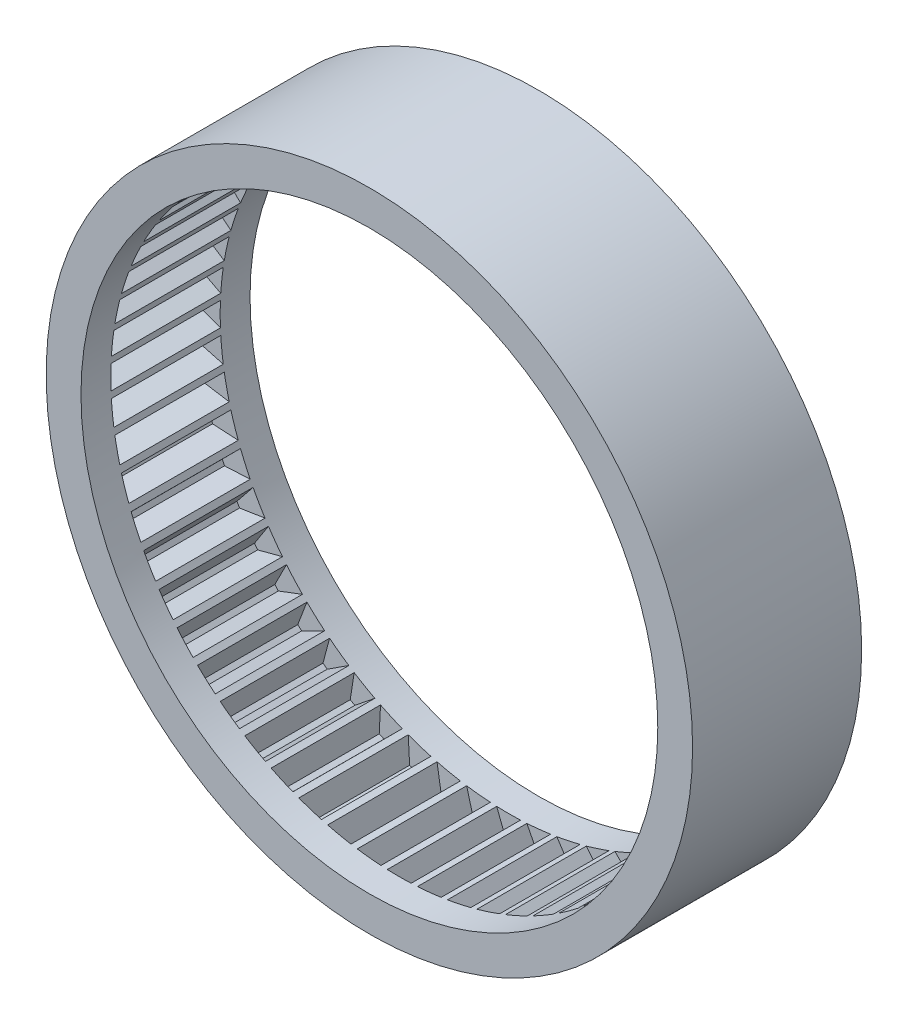
SolidWorks part; units mm, degrees
ref_plane "Front Plane" through (0, 0, 0) normal (0, 0, 1) x (1, 0, 0)
ref_plane "Top Plane" through (0, 0, 0) normal (0, 1, 0) x (1, 0, 0)
ref_plane "Right Plane" through (0, 0, 0) normal (1, 0, 0) x (0, 0, -1)
sketch "Esquisse5" plane through (0, 0, 0) normal (0, 0, 1) x (1, 0, 0)
  circle A0 centre (0, 0) radius 29
  circle A1 centre (0, 0) radius 32.5
  dimension "D1" = 58
  dimension "D2" = 65
extrude "Boss.-Extru.3" add sketch "Esquisse5" against normal blind 17 from offset 18 offset against normal yes
ref_plane "Plan4" through (0, 0, -26.5) normal (0, 0, -1) x (-1, 0, 0)
sketch "Esquisse6" plane through (0, 0, -26.5) normal (0, 0, -1) x (-1, 0, 0)
  line L0 (0, 111.9885) -> (0, -49.2085) construction
  line L1 (1.2196, 28.9208) -> (1.436, 28.9095)
  line L2 (1.436, 28.9095) -> (1.436, 32.2573) construction
  line L3 (1.436, 28.9095) -> (1.436, 28.7372)
  line L4 (1.436, 28.7372) -> (-1.436, 28.7372)
  line L5 (-1.436, 28.7372) -> (-1.436, 28.9095)
  line L6 (-0.2642, 31.39) -> (0.2642, 31.39)
  line L7 (0.2642, 31.39) -> (1.2205, 28.9186)
  line L8 (-0.2642, 31.39) -> (-1.2196, 28.9208)
  line L9 (-1.436, 28.9095) -> (-1.6741, 33.4532) construction
  line L11 (-1.2196, 28.9208) -> (-1.436, 28.9095)
  circle A2 centre (0, 0) radius 29 construction
  point P16 (0, 31.39)
  dimension "D1" = 2.65
  dimension "D2" = 1.3
  dimension "D3" = 31.39
  dimension "D4" = 111.153
  dimension "D5" = 111.153
  dimension "D6" = 114.153
  dimension "D7" = 0.2642
  dimension "D9" = 2.6475
extrude "Enlèv. mat.-Extru.2" cut sketch "Esquisse6" against normal mid plane 11 contours L8 L11 L5 L4 L3 L1 L7 L6 region at (0, 29.7573, -26.5)
ref_axis "Axe2" through (0, 0, -18) along (0, 0, -1)
pattern_circular "Répétition circulaire2" count 60 every 6 about axis through (0, 0, -18) along (0, 0, -1) of "Enlèv. mat.-Extru.2"
